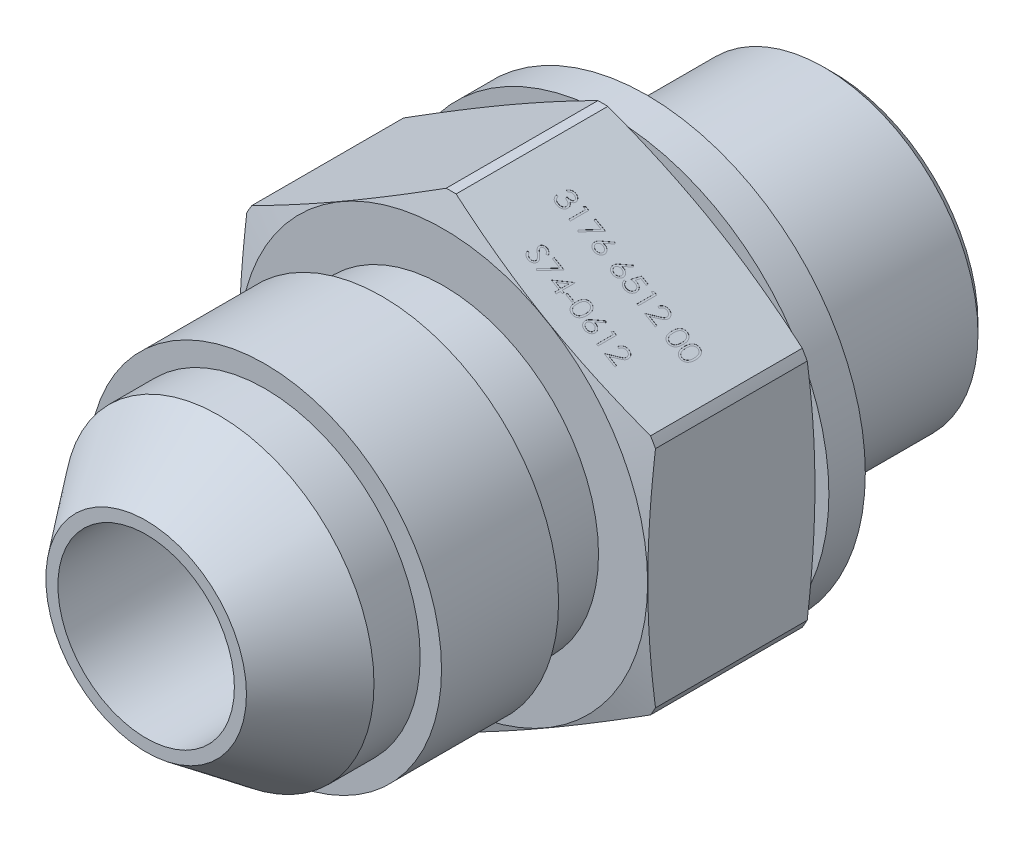
SolidWorks part; units mm, degrees
material "Plain Carbon Steel"
ref_plane "Front Plane" through (0, 0, 0) normal (0, 0, 1) x (1, 0, 0)
ref_plane "Top Plane" through (0, 0, 0) normal (0, 1, 0) x (1, 0, 0)
ref_plane "Right Plane" through (0, 0, 0) normal (1, 0, 0) x (0, 0, -1)
sketch "Sketch1" plane through (0, 0, 0) normal (1, 0, 0) x (0, 0, -1)
  line L0 (0, 0) -> (90.3331, 0) construction
  line L1 (0, 5.4) -> (3.9148, 8.35)
  line L2 (3.9148, 8.35) -> (6.4, 8.35)
  line L3 (6.4, 8.35) -> (6.4, 9.5)
  line L4 (6.4, 9.5) -> (12.7, 9.5)
  line L5 (12.7, 9.5) -> (12.7, 8.35)
  line L6 (12.7, 8.35) -> (16, 8.35)
  line L7 (16, 8.35) -> (16, 10.994)
  line L8 (16.4169, 12.55) -> (24.5831, 12.55)
  line L9 (25, 10.994) -> (25, 8.275)
  line L10 (25, 8.275) -> (36.5, 8.275)
  line L11 (37, 7.775) -> (37, 6.8)
  line L12 (37, 6.8) -> (33.4493, 4.75)
  line L13 (33.4493, 4.75) -> (0, 4.75)
  line L14 (0, 4.75) -> (0, 5.4)
  line L15 (36.5, 8.275) -> (37, 7.775)
  line L16 (16.4169, 12.55) -> (16, 10.994)
  line L17 (24.5831, 12.55) -> (25, 10.994)
  point P14 (37, 8.275)
  dimension "D1" = 25.1
  dimension "D2" = 16.55
  dimension "D3" = 9.5
  dimension "D4" = 13.6
  dimension "D5" = 30
  dimension "D6" = 12
  dimension "D7" = 37
  dimension "D8" = 3.3
  dimension "D9" = 6.4
  dimension "D10" = 16.7
  dimension "D11" = 19
  dimension "D12" = 16
  dimension "D13" = 10.8
  dimension "D14" = 37
  dimension "D15" = 15
  dimension "D16" = 15
  dimension "D18" = 1.556
revolve "Revolve1" add sketch "Sketch1" angle 360 about L0
cosmetic thread "Cosmetic Thread1" parameters "D2"=16.6
sketch "Sketch2" plane through (0, 0, -16) normal (0, 0, 1) x (1, 0, 0)
  line L1 (0, 12.7017) -> (-11, 6.3509)
  line L2 (-11, 6.3509) -> (-11, -6.3509)
  line L3 (-11, -6.3509) -> (0, -12.7017)
  line L4 (0, -12.7017) -> (11, -6.3509)
  line L5 (11, -6.3509) -> (11, 6.3509)
  line L6 (11, 6.3509) -> (0, 12.7017)
  circle A0 centre (0, 0) radius 11 construction
  dimension "D1" = 22
extrude "Extrude2" cut sketch "Sketch2" against normal up to surface (9 mm away) flip side to cut up to face at (10.994, 0, -25)
sketch "Sketch3" plane through (0, 0, -25) normal (0, 0, -1) x (-1, 0, 0)
  circle A0 centre (0, 0) radius 11.75
  circle A1 centre (0, 0) radius 9.9
  dimension "D1" = 23.5
  dimension "D2" = 19.8
extrude "Extrude3" add sketch "Sketch3" along normal blind 1.96
sketch "Sketch5" plane through (5.5, 9.5263, 0) normal (0.5, 0.866, 0) x (0.866, -0.5, 0)
  line L0 (-5.7258, 19.8095) -> (6.0417, 19.8095) construction
  line L1 (6.0417, 16.4169) -> (6.0417, 24.5831) construction
  text T0 "3176 6512 00\r\nS74-0612" font "Century Gothic" height 1
extrude "Cut-Extrude1" cut sketch "Sketch5" against normal blind 0.01
sketch "Sketch6" plane through (0, 0, 0) normal (1, 0, 0) x (0, 0, -1)
  line L0 (0, 0) -> (40.5913, 0) construction
  line L1 (26.96, -11.75) -> (26.96, 11.75) construction
  circle A0 centre (26.16, 9) radius 1.2
  dimension "D1" = 18
  dimension "D2" = 2.4
  dimension "D3" = 0.8
revolve "Revolve2" add sketch "Sketch6" angle 360 about L0
